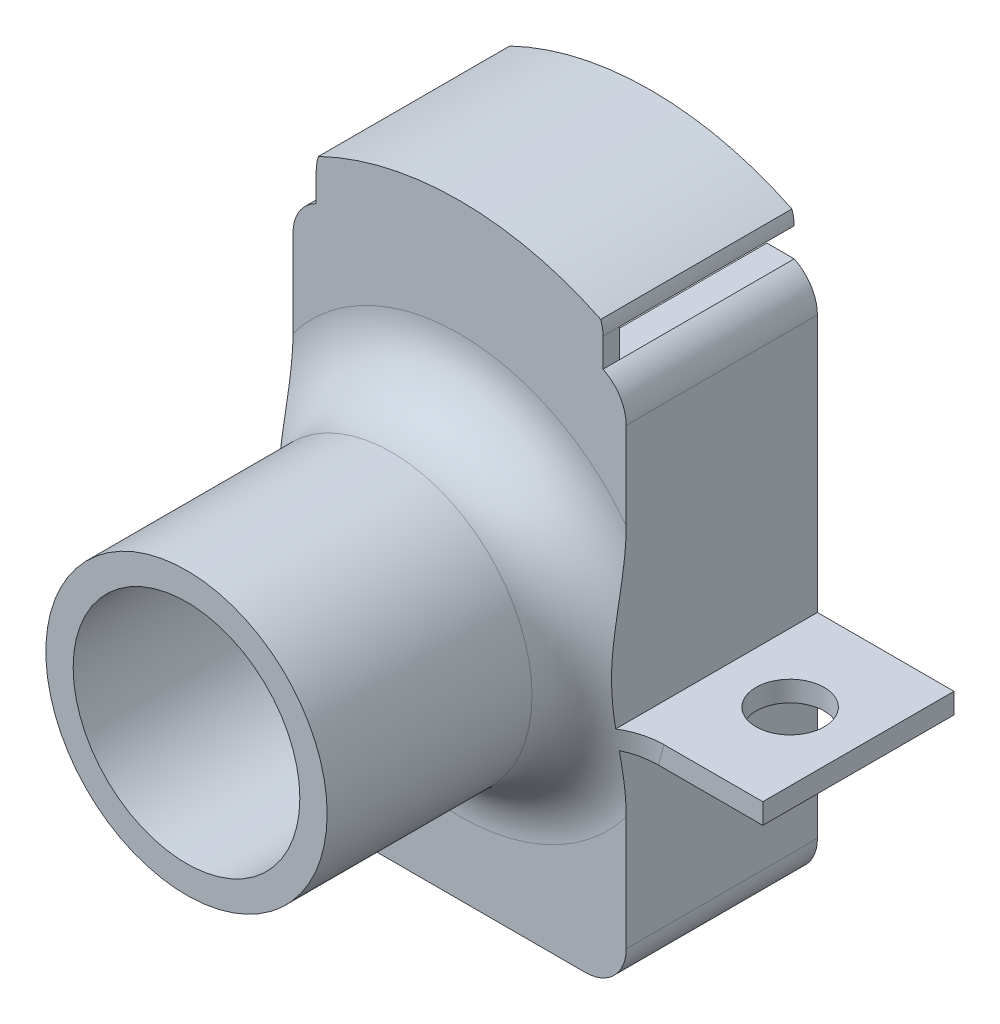
SolidWorks part; units mm, degrees
ref_plane "Front Plane" through (0, 0, 0) normal (0, 0, 1) x (1, 0, 0)
ref_plane "Top Plane" through (0, 0, 0) normal (0, 1, 0) x (1, 0, 0)
ref_plane "Right Plane" through (0, 0, 0) normal (1, 0, 0) x (0, 0, -1)
sketch "Sketch1" plane through (0, 0, 0) normal (1, 0, 0) x (0, 0, -1)
  line L0 (0, 0) -> (59.0662, 0) construction
  line L1 (0, 10.541) -> (25.4, 10.541)
  line L2 (25.4, 10.541) -> (25.4, 6.564)
  line L3 (25.4, 6.564) -> (43.18, 6.564)
  line L4 (43.18, 6.564) -> (43.18, 30.1625)
  line L5 (43.18, 30.1625) -> (25.4, 30.1625)
  line L6 (25.4, 30.1625) -> (25.4, 19.431)
  line L7 (19.05, 13.081) -> (0, 13.081)
  line L8 (0, 13.081) -> (0, 10.541)
  line L10 (43.18, 0) -> (26.924, 0) construction
  line L11 (43.18, 0) -> (43.18, 26.0812) construction
  line L12 (43.18, 26.0812) -> (26.924, 26.0812) construction
  line L13 (26.924, 0) -> (26.924, 26.0812) construction
  arc A0 (25.4, 19.431) -> (19.05, 13.081) centre (19.05, 19.431) cw
  dimension "D4" = 6.35
  dimension "D1" = 21.082
  dimension "D2" = 2.54
  dimension "D3" = 25.4
  dimension "D5" = 43.18
  dimension "D6" = 60.325
  dimension "D7" = 16.256
revolve "Body" add sketch "Sketch1" angle 360 about L0
sketch "Sketch2" plane through (0, 0, -43.18) normal (0, 0, -1) x (-1, 0, 0)
  line L0 (0, -1.27) -> (0, 27.178) construction
  line L1 (-11.684, -23.622) -> (11.684, -23.622)
  line L2 (-12.954, -22.352) -> (-12.954, 19.812)
  line L3 (-11.684, 21.082) -> (-10.795, 21.082)
  line L4 (12.954, -22.352) -> (12.954, 19.812)
  line L5 (-12.954, -23.622) -> (12.954, 21.082) construction
  line L6 (-12.954, 21.082) -> (12.954, -23.622) construction
  line L7 (-15.494, -22.352) -> (-15.494, -6.0601)
  line L8 (-13.335, 23.2457) -> (-13.335, 23.2457)
  line L9 (-9.525, 27.178) -> (9.525, 27.178)
  line L10 (-13.335, 23.2457) -> (-13.335, 25.908)
  line L11 (-10.795, 21.082) -> (-10.795, 25.908)
  line L12 (10.795, 21.082) -> (11.684, 21.082)
  line L13 (10.795, 21.082) -> (10.795, 25.908)
  line L14 (-9.525, 29.718) -> (9.525, 29.718)
  line L15 (13.335, 23.2457) -> (13.335, 25.908)
  line L16 (13.335, 23.2457) -> (13.335, 23.2457)
  line L17 (15.494, -22.352) -> (15.494, 19.812)
  line L18 (-11.684, -26.162) -> (11.684, -26.162)
  line L19 (-15.494, -4.1551) -> (-15.494, 19.812)
  line L20 (-28.194, -4.1551) -> (-15.494, -4.1551)
  line L21 (-28.194, -4.1551) -> (-28.194, -6.0601)
  line L22 (-28.194, -6.0601) -> (-15.494, -6.0601)
  line L23 (-13.335, 25.908) -> (-10.795, 25.908)
  line L24 (-15.494, -22.352) -> (-15.494, 19.812) construction
  line L25 (-13.335, 23.2457) -> (-10.795, 23.2457)
  circle A0 centre (0, 0) radius 28.8925 construction
  circle A1 centre (0, 0) radius 30.1625 construction
  arc A2 (-11.684, 21.082) -> (-12.954, 19.812) centre (-11.684, 19.812) ccw
  arc A3 (-9.525, 27.178) -> (-10.795, 25.908) centre (-9.525, 25.908) ccw
  arc A4 (9.525, 27.178) -> (10.795, 25.908) centre (9.525, 25.908) cw
  arc A5 (11.684, 21.082) -> (12.954, 19.812) centre (11.684, 19.812) cw
  arc A6 (12.954, -22.352) -> (11.684, -23.622) centre (11.684, -22.352) cw
  arc A7 (-11.684, -23.622) -> (-12.954, -22.352) centre (-11.684, -22.352) cw
  arc A8 (-13.335, 23.2457) -> (-15.494, 19.812) centre (-11.684, 19.812) ccw
  arc A9 (-9.525, 29.718) -> (-13.335, 25.908) centre (-9.525, 25.908) ccw
  arc A10 (9.525, 29.718) -> (13.335, 25.908) centre (9.525, 25.908) cw
  arc A11 (13.335, 23.2457) -> (15.494, 19.812) centre (11.684, 19.812) cw
  arc A12 (15.494, -22.352) -> (11.684, -26.162) centre (11.684, -22.352) cw
  arc A13 (-11.684, -26.162) -> (-15.494, -22.352) centre (-11.684, -22.352) cw
  point P0 (0, -1.27)
  point P21 (-10.795, 27.178)
  point P24 (10.795, 27.178)
  circle M7 centre (0, 0) radius 30.1625
  circle M8 centre (0, 0) radius 6.564
  dimension "D5" = 1.27
  dimension "D8" = 1.27
  dimension "D1" = 44.704
  dimension "D2" = 25.908
  dimension "D3" = 50.8
  dimension "D4" = 21.59
  dimension "D6" = 1.27
  dimension "D7" = 6.096
  dimension "D10" = 12.7
  dimension "D11" = 1.905
  dimension "D9" = 2.54
extrude "Battery holder" cut sketch "Sketch2" against normal blind 16.256 contours A7 L1 A6 L4 A5 L12 L13 A4 L9 A3 L11 L3 A2 L2 M8 | L10 L25 L11 L23 region at (12.1788, -22.8468, -43.18) region at (12.065, 24.5769, -43.18)
extrude "Cut-Extrude3" cut sketch "Sketch2<3>" against normal blind 26.416 contours L18 A13 L7 L22 L21 L20 L19 A8 L10 A9 A10 L15 A11 L17 A12 M7 region at (15.6139, 22.283, -43.18)
sketch "Sketch2<3>" plane through (0, 0, -43.18) normal (0, 0, -1) x (-1, 0, 0) same geometry as "Sketch2"
sketch "Sketch3" plane through (0, -6.0601, 0) normal (0, -1, 0) x (1, 0, 0)
  line L0 (28.194, -43.18) -> (15.494, -25.4) construction
  line L3 (15.494, -24.7523) -> (15.494, -43.18) construction
  line L4 (28.194, -25.4) -> (18.4618, -25.4) construction
  circle A0 centre (21.844, -34.29) radius 3.175
  dimension "D1" = 6.35
extrude "Panel Mount" cut sketch "Sketch3" against normal blind 16.256
